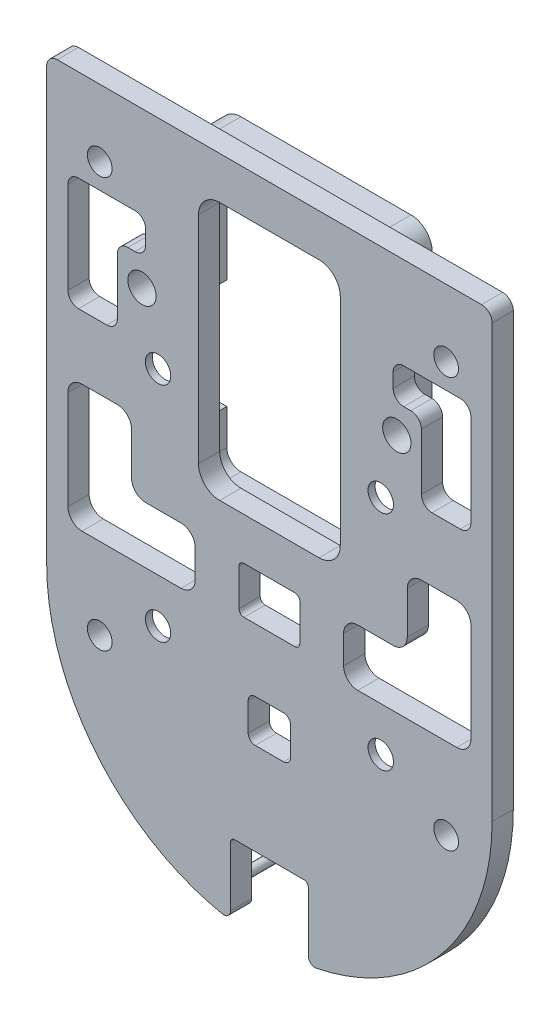
SolidWorks part; units mm, degrees
ref_plane "Alzado" through (0, 0, 0) normal (0, 0, 1) x (1, 0, 0)
ref_plane "Planta" through (0, 0, 0) normal (0, 1, 0) x (1, 0, 0)
ref_plane "Vista lateral" through (0, 0, 0) normal (1, 0, 0) x (0, 0, -1)
sketch "Croquis1" plane through (0, 0, 0) normal (0, 0, 1) x (1, 0, 0)
  line L0 (-31.5, 0) -> (31.5, 0) construction
  line L1 (31.5, -46.5) -> (-31.5, -46.5)
  line L2 (31.5, -45) -> (31.5, 45)
  line L3 (30, 46.5) -> (-30, 46.5)
  line L4 (-31.5, -45) -> (-31.5, 45)
  line L5 (-31.5, -45) -> (-31.5, -46.5)
  line L7 (17.25, -17.25) -> (-17.25, -17.25) construction
  line L8 (17.25, -17.25) -> (17.25, 17.25) construction
  line L9 (17.25, 17.25) -> (-17.25, 17.25) construction
  line L10 (-17.25, -17.25) -> (-17.25, 17.25) construction
  line L11 (17.25, -17.25) -> (-17.25, 17.25) construction
  line L12 (17.25, 17.25) -> (-17.25, -17.25) construction
  line L13 (31.5, -45) -> (31.5, -46.5)
  line L14 (0, 46.5) -> (0, -46.5) construction
  circle A0 centre (-15.75, 15.75) radius 1.5
  arc A6 (31.5, 45) -> (30, 46.5) centre (30, 45) ccw
  arc A7 (-31.5, 45) -> (-30, 46.5) centre (-30, 45) cw
  circle A8 centre (15.75, 15.75) radius 1.5
  circle A9 centre (-15.75, -15.75) radius 1.5
  circle A10 centre (15.75, -15.75) radius 1.5
  point P0 (0, 0)
  point P6 (0, 0)
  point P13 (-15.75, 17.25)
  point P14 (-17.25, 15.75)
  point P15 (-17.25, 15.75)
  point P16 (0, 0)
  point P38 (0, 0)
  dimension "D4" = 3
  dimension "D5" = 31.5
  dimension "D7" = 1.5
  dimension "D1" = 60
  dimension "D2" = 31.5
  dimension "D3" = 90
  dimension "D6" = 93
extrude "Saliente-Extruir1" add sketch "Croquis1" along normal blind 3
sketch "Croquis3" plane through (0, 0, 3) normal (0, 0, 1) x (1, 0, 0)
  line L0 (0, 46.5) -> (0, -46.5) construction
  line L1 (2, -17.5) -> (-2, -17.5)
  line L2 (-9, -45.5) -> (9, -45.5) construction
  line L3 (-9, -45.5) -> (-9, -2.3) construction
  line L4 (-9, -2.3) -> (9, -2.3) construction
  line L5 (9, -45.5) -> (9, -2.3) construction
  line L7 (0, -2.3) -> (0, -45.5) construction
  line L8 (-3.6, -2.3) -> (3.6, -2.3)
  line L9 (-4, -2.7) -> (-4, -7.9)
  line L10 (-3.6, -8.3) -> (3.6, -8.3)
  line L11 (4, -2.7) -> (4, -7.9)
  line L12 (-9, -23.9) -> (9, -23.9) construction
  line L13 (-31.5, -46.5) -> (31.5, -46.5) construction
  line L14 (3, -18.5) -> (3, -22.5)
  line L15 (-4.9, -47.5) -> (4.9, -47.5)
  line L16 (-5.5, -46.9) -> (-5.5, -37.1)
  line L17 (-4.9, -36.5) -> (4.9, -36.5)
  line L18 (5.5, -46.9) -> (5.5, -37.1)
  line L19 (2, -23.5) -> (-2, -23.5)
  line L20 (-3, -18.5) -> (-3, -22.5)
  line L24 (-31.5, -46.5) -> (31.5, -46.5)
  line L25 (-31.5, 45) -> (-31.5, -46.5)
  line L26 (30, 46.5) -> (-30, 46.5)
  line L27 (31.5, -46.5) -> (31.5, 45)
  line L28 (-31.5, -46.5) -> (31.5, -46.5) construction
  line L29 (-31.5, 45) -> (-31.5, -46.5) construction
  line L30 (30, 46.5) -> (-30, 46.5) construction
  line L31 (31.5, -46.5) -> (31.5, 45) construction
  circle A0 centre (-7.62, -3.68) radius 0.65
  circle A1 centre (7.62, -3.68) radius 0.65
  circle A2 centre (-7.62, -44.12) radius 0.65
  circle A3 centre (7.62, -44.12) radius 0.65
  arc A4 (4, -2.7) -> (3.6, -2.3) centre (3.6, -2.7) ccw
  arc A5 (4, -7.9) -> (3.6, -8.3) centre (3.6, -7.9) cw
  arc A6 (-3.6, -8.3) -> (-4, -7.9) centre (-3.6, -7.9) cw
  arc A7 (-4, -2.7) -> (-3.6, -2.3) centre (-3.6, -2.7) cw
  arc A8 (-5.5, -37.1) -> (-4.9, -36.5) centre (-4.9, -37.1) cw
  arc A9 (4.9, -36.5) -> (5.5, -37.1) centre (4.9, -37.1) cw
  arc A10 (5.5, -46.9) -> (4.9, -47.5) centre (4.9, -46.9) cw
  arc A11 (-4.9, -47.5) -> (-5.5, -46.9) centre (-4.9, -46.9) cw
  arc A12 (-3, -18.5) -> (-2, -17.5) centre (-2, -18.5) cw
  arc A13 (-2, -23.5) -> (-3, -22.5) centre (-2, -22.5) cw
  arc A14 (3, -22.5) -> (2, -23.5) centre (2, -22.5) cw
  arc A15 (3, -18.5) -> (2, -17.5) centre (2, -18.5) ccw
  arc A22 (-30, 46.5) -> (-31.5, 45) centre (-30, 45) ccw
  arc A23 (31.5, 45) -> (30, 46.5) centre (30, 45) ccw
  arc A26 (-30, 46.5) -> (-31.5, 45) centre (-30, 45) ccw construction
  arc A27 (31.5, 45) -> (30, 46.5) centre (30, 45) ccw construction
  point P16 (0, -2.3)
  point P35 (-4, -2.3)
  point P42 (5.5, -36.5)
  point P45 (5.5, -47.5)
  point P48 (-5.5, -47.5)
  line M6 (-31.5, -46.5) -> (31.5, -46.5)
  dimension "D6" = 1.3
  dimension "D9" = 0.4
  dimension "D15" = 0.6
  dimension "D16" = 0.6
  dimension "D21" = 1
  dimension "D1" = 1
  dimension "D2" = 18
  dimension "D4" = 6
  dimension "D5" = 8
  dimension "D7" = 1.38
  dimension "D8" = 1.38
  dimension "D10" = 43.2
  dimension "D11" = 11
  dimension "D12" = 9
  dimension "D13" = 11
  dimension "D14" = 5.5
  dimension "D17" = 28
  dimension "D18" = 12
  dimension "D19" = 22
  dimension "D20" = 12
  dimension "D22" = 0
extrude "Cortar-Extruir1" cut sketch "Croquis3" against normal through all contours A3 | L11 L8 L9 L10 | A11 L15 A10 L18 L16 M6 | A9 L17 A8 L16 L18 M6 | A2 | A0 | A1 | L19 A13 L20 A12 L1 A15 L14 A14 region at (0, -5.3, 3) region at (0, -46.9948, 3) region at (0, -41.5068, 3) region at (7.62, -44.12, 3)
sketch "Croquis5" plane through (0, 0, 3) normal (0, 0, 1) x (1, 0, 0)
  line L12 (4, -2.7) -> (4, -7.9) construction
  line L13 (-3.6, -2.3) -> (3.6, -2.3) construction
  line L14 (-4, -2.7) -> (-4, -7.9) construction
  line L15 (-3.6, -8.3) -> (3.6, -8.3) construction
  line L16 (4, -2.7) -> (4, -7.9)
  line L17 (-3.6, -2.3) -> (3.6, -2.3)
  line L18 (-4, -2.7) -> (-4, -7.9)
  line L19 (-3.6, -8.3) -> (3.6, -8.3)
  line L20 (4.3, -2.7) -> (4.3, -7.9)
  line L21 (-3.6, -8.6) -> (3.6, -8.6)
  line L22 (-4.3, -2.7) -> (-4.3, -7.9)
  line L23 (-3.6, -2) -> (3.6, -2)
  circle A0 centre (7.62, -44.12) radius 0.65 construction
  circle A1 centre (-7.62, -44.12) radius 0.65 construction
  circle A8 centre (7.62, -44.12) radius 0.65
  circle A9 centre (-7.62, -44.12) radius 0.65
  arc A37 (4, -2.7) -> (3.6, -2.3) centre (3.6, -2.7) ccw construction
  arc A38 (3.6, -8.3) -> (4, -7.9) centre (3.6, -7.9) ccw construction
  arc A39 (-4, -7.9) -> (-3.6, -8.3) centre (-3.6, -7.9) ccw construction
  arc A40 (-3.6, -2.3) -> (-4, -2.7) centre (-3.6, -2.7) ccw construction
  circle A41 centre (-7.62, -3.68) radius 0.65 construction
  circle A42 centre (7.62, -3.68) radius 0.65 construction
  circle A43 centre (-15.75, -15.75) radius 1.5 construction
  circle A44 centre (15.75, -15.75) radius 1.5 construction
  circle A45 centre (15.75, 15.75) radius 1.5 construction
  circle A46 centre (-15.75, 15.75) radius 1.5 construction
  arc A47 (4, -2.7) -> (3.6, -2.3) centre (3.6, -2.7) ccw
  arc A48 (3.6, -8.3) -> (4, -7.9) centre (3.6, -7.9) ccw
  arc A49 (-4, -7.9) -> (-3.6, -8.3) centre (-3.6, -7.9) ccw
  arc A50 (-3.6, -2.3) -> (-4, -2.7) centre (-3.6, -2.7) ccw
  circle A51 centre (-7.62, -3.68) radius 0.65
  circle A52 centre (7.62, -3.68) radius 0.65
  circle A53 centre (-15.75, -15.75) radius 1.5
  circle A54 centre (15.75, -15.75) radius 1.5
  circle A55 centre (15.75, 15.75) radius 1.5
  circle A56 centre (-15.75, 15.75) radius 1.5
  arc A57 (3.6, -8.6) -> (4.3, -7.9) centre (3.6, -7.9) ccw
  arc A58 (-4.3, -7.9) -> (-3.6, -8.6) centre (-3.6, -7.9) ccw
  arc A59 (-3.6, -2) -> (-4.3, -2.7) centre (-3.6, -2.7) ccw
  arc A60 (4.3, -2.7) -> (3.6, -2) centre (3.6, -2.7) ccw
  circle A63 centre (-15.75, -15.75) radius 1.8
  circle A64 centre (15.75, -15.75) radius 1.8
  circle A65 centre (15.75, 15.75) radius 1.8
  circle A66 centre (-15.75, 15.75) radius 1.8
  dimension "D1" = 0.3
extrude "Cortar-Extruir3" cut sketch "Croquis5" against normal through all
fillet "Redondeo1" radius 1 2 edges at (5.5, -46.5, 1.5) (-5.5, -46.5, 1.5)
sketch "Croquis14" plane through (0, 0, 0) normal (0, 0, -1) x (-1, 0, 0)
  circle A0 centre (7.62, -44.12) radius 0.65 construction
  circle A1 centre (-7.62, -44.12) radius 0.65 construction
  circle A2 centre (7.62, -3.68) radius 0.65 construction
  circle A3 centre (-7.62, -3.68) radius 0.65 construction
  circle A4 centre (7.62, -44.12) radius 0.65
  circle A5 centre (-7.62, -44.12) radius 0.65
  circle A6 centre (7.62, -3.68) radius 0.65
  circle A7 centre (-7.62, -3.68) radius 0.65
extrude "Saliente-Extruir2" add sketch "Croquis14" along normal blind 5 and the other way up to surface (3 mm away) other way up to face at (0, -5.3, 3)
sketch "Croquis18" plane through (0, 0, 0) normal (0, 0, -1) x (-1, 0, 0)
  line L0 (0, 46.5) -> (0, -46.5) construction
  line L1 (12.025, 1) -> (-12.025, 1)
  line L2 (14.025, 3) -> (14.025, 41.5)
  line L3 (12.025, 43.5) -> (-12.025, 43.5)
  line L4 (-14.025, 3) -> (-14.025, 41.5)
  line L5 (14.025, 1) -> (-14.025, 43.5) construction
  line L6 (14.025, 43.5) -> (-14.025, 1) construction
  line L7 (-15.025, 3) -> (-15.025, 41.5)
  line L8 (12.025, 44.5) -> (-12.025, 44.5)
  line L9 (15.025, 3) -> (15.025, 41.5)
  line L10 (12.025, 0) -> (-12.025, 0)
  line L11 (-30, 46.5) -> (30, 46.5) construction
  arc A0 (12.025, 43.5) -> (14.025, 41.5) centre (12.025, 41.5) cw
  arc A1 (14.025, 3) -> (12.025, 1) centre (12.025, 3) cw
  arc A2 (-12.025, 1) -> (-14.025, 3) centre (-12.025, 3) cw
  arc A3 (-12.025, 43.5) -> (-14.025, 41.5) centre (-12.025, 41.5) ccw
  arc A4 (-12.025, 44.5) -> (-15.025, 41.5) centre (-12.025, 41.5) ccw
  arc A5 (12.025, 44.5) -> (15.025, 41.5) centre (12.025, 41.5) cw
  arc A6 (15.025, 3) -> (12.025, 0) centre (12.025, 3) cw
  arc A7 (-12.025, 0) -> (-15.025, 3) centre (-12.025, 3) cw
  point P0 (0, 22.25)
  dimension "D3" = 2
  dimension "D1" = 28.05
  dimension "D2" = 42.5
  dimension "D5" = 2
  dimension "D4" = 1
extrude "Saliente-Extruir3" add sketch "Croquis18" along normal blind 5
sketch "Croquis22" plane through (0, 0, 0) normal (0, 0, -1) x (-1, 0, 0)
  line L0 (-14.025, 41.5) -> (-14.025, 16.2642) construction
  line L1 (12.025, 43.5) -> (-12.025, 43.5) construction
  line L2 (-12.025, 1) -> (12.025, 1) construction
  line L3 (14.025, 3) -> (14.025, 15.2358) construction
  line L4 (-14.025, 41.5) -> (-14.025, 16.2642) construction
  line L5 (12.025, 43.5) -> (-12.025, 43.5) construction
  line L6 (-12.025, 1) -> (12.025, 1) construction
  line L7 (14.025, 3) -> (14.025, 15.2358) construction
  line L8 (18.025, 24.5) -> (-18.025, 24.5) construction
  line L9 (15.025, 3) -> (15.025, 14.1025) construction
  line L10 (-15.025, 41.5) -> (-15.025, 17.3975) construction
  circle A0 centre (18.025, 24.5) radius 2
  circle A1 centre (-18.025, 24.5) radius 2
  dimension "D1" = 4
  dimension "D2" = 4
  dimension "D3" = 3
  dimension "D4" = 3
  dimension "D5" = 19
extrude "Cortar-Extruir14" cut sketch "Croquis22" against normal blind 30
sketch "Croquis16" plane through (0, 0, 0) normal (0, 0, -1) x (-1, 0, 0)
  circle A0 centre (15.75, -15.75) radius 1.8 construction
  circle A1 centre (-15.75, -15.75) radius 1.8 construction
  circle A2 centre (-15.75, 15.75) radius 1.8 construction
  circle A3 centre (15.75, 15.75) radius 1.8 construction
  circle A4 centre (15.75, -15.75) radius 1.8
  circle A5 centre (-15.75, -15.75) radius 1.8
  circle A6 centre (-15.75, 15.75) radius 1.8
  circle A7 centre (15.75, 15.75) radius 1.8
  circle A8 centre (15.75, -15.75) radius 4.8
  circle A9 centre (-15.75, -15.75) radius 4.8
  circle A10 centre (-15.75, 15.75) radius 4.8
  circle A11 centre (15.75, 15.75) radius 4.8
  dimension "D1" = 3
extrude "Cortar-Extruir9" cut sketch "Croquis16" against normal blind 2 and the other way blind 30
sketch "Croquis23" plane through (0, 0, -5) normal (0, 0, -1) x (-1, 0, 0)
  line L0 (15.025, 23.4949) -> (-15.025, 23.4949) construction
  line L1 (15.025, 20.4949) -> (15.025, 41.5) construction
  line L2 (-15.025, 41.5) -> (-15.025, 20.4949) construction
  line L3 (-15.025, 23.4949) -> (-15.025, 16.6219) construction
  line L4 (-15.025, 11.0051) -> (-15.025, 3) construction
  line L5 (-15.025, 8.0051) -> (15.025, 8.0051) construction
  line L6 (15.025, 3) -> (15.025, 11.0051) construction
  line L7 (15.025, 8.0051) -> (15.025, 14.8781) construction
  line L8 (-14.025, 8.0051) -> (-15.025, 8.0051)
  line L9 (-14.025, 20.2293) -> (-14.025, 41.5) construction
  line L10 (-15.025, 17.3975) -> (-15.025, 14.1025) construction
  line L11 (14.025, 41.5) -> (14.025, 20.2293) construction
  line L12 (14.025, 11.2707) -> (14.025, 3) construction
  line L13 (-14.025, 15.2358) -> (-14.025, 16.2642) construction
  line L14 (-14.025, 3) -> (-14.025, 11.2707) construction
  line L15 (14.025, 16.2642) -> (14.025, 15.2358) construction
  line L16 (15.025, 20.4949) -> (15.025, 23.4949)
  line L18 (-15.025, 23.4949) -> (-15.025, 20.4949)
  line L19 (-14.025, 20.2293) -> (-14.025, 23.4949)
  line L21 (14.025, 23.4949) -> (14.025, 20.2293)
  line L22 (14.025, 11.2707) -> (14.025, 8.0051)
  line L24 (-14.025, 8.0051) -> (-14.025, 11.2707)
  line L25 (-15.025, 11.0051) -> (-15.025, 8.0051)
  line L27 (15.025, 8.0051) -> (15.025, 11.0051)
  line L28 (15.025, 8.0051) -> (14.025, 8.0051)
  line L29 (15.025, 23.4949) -> (14.025, 23.4949)
  line L30 (-14.025, 23.4949) -> (-15.025, 23.4949)
  line L31 (15.025, 14.1025) -> (15.025, 17.3975) construction
  line L36 (15.025, 16.9698) -> (15.025, 23.4949) construction
  line L37 (-15.025, 14.5302) -> (-15.025, 8.0051) construction
  line L42 (-15.025, 17.3975) -> (-15.025, 14.1025)
  line L43 (-14.025, 15.2358) -> (-14.025, 16.2642)
  line L44 (14.025, 16.2642) -> (14.025, 15.2358)
  line L45 (15.025, 14.1025) -> (15.025, 17.3975)
  arc A0 (15.025, 20.4949) -> (14.025, 20.2293) centre (15.75, 15.75) ccw construction
  arc A1 (-15.025, 14.1025) -> (-14.025, 15.2358) centre (-15.75, 15.75) ccw construction
  arc A2 (-14.025, 16.2642) -> (-15.025, 17.3975) centre (-15.75, 15.75) ccw construction
  arc A3 (-14.025, 20.2293) -> (-15.025, 20.4949) centre (-15.75, 15.75) ccw construction
  arc A4 (14.025, 15.2358) -> (15.025, 14.1025) centre (15.75, 15.75) ccw construction
  arc A5 (15.025, 17.3975) -> (14.025, 16.2642) centre (15.75, 15.75) ccw construction
  arc A6 (14.025, 11.2707) -> (15.025, 11.0051) centre (15.75, 15.75) ccw construction
  arc A9 (-15.025, 11.0051) -> (-14.025, 11.2707) centre (-15.75, 15.75) ccw construction
  arc A12 (15.025, 20.4949) -> (14.025, 20.2293) centre (15.75, 15.75) ccw
  arc A15 (-14.025, 20.2293) -> (-15.025, 20.4949) centre (-15.75, 15.75) ccw
  arc A18 (14.025, 11.2707) -> (15.025, 11.0051) centre (15.75, 15.75) ccw
  arc A21 (-15.025, 11.0051) -> (-14.025, 11.2707) centre (-15.75, 15.75) ccw
  arc A26 (-15.025, 14.1025) -> (-14.025, 15.2358) centre (-15.75, 15.75) ccw
  arc A27 (-14.025, 16.2642) -> (-15.025, 17.3975) centre (-15.75, 15.75) ccw
  arc A28 (14.025, 15.2358) -> (15.025, 14.1025) centre (15.75, 15.75) ccw
  arc A29 (15.025, 17.3975) -> (14.025, 16.2642) centre (15.75, 15.75) ccw
  dimension "D1" = 3
  dimension "D2" = 3
extrude "Cortar-Extruir15" cut sketch "Croquis23" against normal up to surface (5 mm away) up to face at (-10.95, -15.75, 0)
sketch "Croquis11" plane through (0, 0, 3) normal (0, 0, 1) x (1, 0, 0)
  line L0 (0.5, 14.5) -> (0.5, -22.5) construction
  line L1 (-25.5, 8) -> (26.5, 8) construction
  line L2 (-31.5, -46.5) -> (31.5, -46.5) construction
  line L3 (-25.5, 38.5) -> (26.5, 38.5) construction
  line L4 (-25.5, 38.5) -> (-25.5, -22.5) construction
  line L5 (-25.5, -22.5) -> (26.5, -22.5) construction
  line L6 (26.5, 38.5) -> (26.5, -22.5) construction
  line L8 (-31.5, 45) -> (-31.5, -46.5) construction
  line L9 (-25.5, 38.5) -> (-28, 38.5) construction
  line L10 (-25.5, 38.5) -> (-25.5, 23) construction
  circle A1 centre (-24, 37) radius 1.5 construction
  circle A2 centre (25, 37) radius 1.5 construction
  circle A3 centre (25, -21) radius 1.5 construction
  circle A8 centre (-24, -21) radius 1.5 construction
  circle A12 centre (-24, 37) radius 1.75
  circle A14 centre (25, -21) radius 1.75
  circle A15 centre (25, 37) radius 1.75
  circle A16 centre (-24, -21) radius 1.75
  point P10 (0.5, -4)
  point P15 (0.5, 38.5)
  point P24 (-24, 38.5)
  point P28 (-3.25, 24.75)
  point P29 (-25.5, 37)
  dimension "D7" = 0.25
  dimension "D6" = 3
  dimension "D1" = 58
  dimension "D2" = 52
  dimension "D3" = 85
  dimension "D4" = 6
  dimension "D5" = 0.25
  dimension "D8" = 0.25
  dimension "D9" = 0.25
extrude "Cortar-Extruir6" cut sketch "Croquis11" against normal blind 52 contours A15 | A14 | A16 | A12
sketch "Croquis24" plane through (0, 0, 0) normal (0, 0, -1) x (-1, 0, 0)
  line L0 (-12.025, 1) -> (12.025, 1) construction
  line L1 (7.025, 4) -> (-7.025, 4)
  line L2 (10.025, 7) -> (10.025, 37.5)
  line L3 (7.025, 40.5) -> (-7.025, 40.5)
  line L4 (-10.025, 7) -> (-10.025, 37.5)
  line L5 (26.5, -9.5) -> (12.5, -9.5)
  line L6 (28.5, -7.5) -> (28.5, -3.4761)
  line L7 (17.5, -1.5) -> (12.5, -1.5)
  line L8 (10.5, -7.5) -> (10.5, -3.5)
  line L10 (28.5, -3.4761) -> (28.5, 6.5)
  line L11 (26.5, 8.5) -> (21.5, 8.5)
  line L12 (19.5, 0.5) -> (19.5, 6.5)
  line L21 (14.025, 3) -> (14.025, 8.0051) construction
  line L22 (-14.025, 8.0051) -> (-14.025, 3) construction
  line L23 (12.025, 43.5) -> (-12.025, 43.5) construction
  line L25 (31.5, 45) -> (31.5, -46.5) construction
  line L28 (0, -47.0419) -> (0, 46.5) construction
  line L29 (-30, 46.5) -> (30, 46.5) construction
  line L30 (-28.5, 32) -> (-28.5, 19)
  line L31 (-27, 17.5) -> (-23, 17.5)
  line L32 (-21.5, 19) -> (-21.5, 27)
  line L33 (-20, 28.5) -> (-19, 28.5)
  line L34 (-17.5, 30) -> (-17.5, 32)
  line L35 (-19, 33.5) -> (-27, 33.5)
  line L37 (19, 33.5) -> (27, 33.5)
  line L38 (-26.5, -9.5) -> (-12.5, -9.5)
  line L39 (-10.5, -7.5) -> (-10.5, -3.5)
  line L40 (-17.5, -1.5) -> (-12.5, -1.5)
  line L41 (-19.5, 0.5) -> (-19.5, 6.5)
  line L42 (-26.5, 8.5) -> (-21.5, 8.5)
  line L43 (-28.5, -3.4761) -> (-28.5, 6.5)
  line L44 (-28.5, -7.5) -> (-28.5, -3.4761)
  line L45 (0, 46.5) -> (0, -46.5) construction
  line L46 (17.5, 30) -> (17.5, 32)
  line L47 (20, 28.5) -> (19, 28.5)
  line L48 (21.5, 19) -> (21.5, 27)
  line L49 (27, 17.5) -> (23, 17.5)
  line L50 (28.5, 32) -> (28.5, 19)
  arc A0 (-10.025, 7) -> (-7.025, 4) centre (-7.025, 7) ccw
  arc A1 (-10.025, 37.5) -> (-7.025, 40.5) centre (-7.025, 37.5) cw
  arc A2 (7.025, 40.5) -> (10.025, 37.5) centre (7.025, 37.5) cw
  arc A3 (10.025, 7) -> (7.025, 4) centre (7.025, 7) cw
  arc A4 (-28.5, 32) -> (-27, 33.5) centre (-27, 32) cw
  arc A5 (-17.5, 32) -> (-19, 33.5) centre (-19, 32) ccw
  arc A6 (-19, 28.5) -> (-17.5, 30) centre (-19, 30) ccw
  arc A7 (-21.5, 27) -> (-20, 28.5) centre (-20, 27) cw
  arc A8 (-23, 17.5) -> (-21.5, 19) centre (-23, 19) ccw
  arc A9 (26.5, -9.5) -> (28.5, -7.5) centre (26.5, -7.5) ccw
  arc A10 (26.5, 8.5) -> (28.5, 6.5) centre (26.5, 6.5) cw
  arc A11 (21.5, 8.5) -> (19.5, 6.5) centre (21.5, 6.5) ccw
  arc A12 (19.5, 0.5) -> (17.5, -1.5) centre (17.5, 0.5) cw
  arc A13 (10.5, -3.5) -> (12.5, -1.5) centre (12.5, -3.5) cw
  arc A14 (10.5, -7.5) -> (12.5, -9.5) centre (12.5, -7.5) ccw
  arc A15 (-28.5, 19) -> (-27, 17.5) centre (-27, 19) ccw
  arc A16 (28.5, 19) -> (27, 17.5) centre (27, 19) cw
  arc A17 (23, 17.5) -> (21.5, 19) centre (23, 19) cw
  arc A18 (21.5, 27) -> (20, 28.5) centre (20, 27) ccw
  arc A19 (19, 28.5) -> (17.5, 30) centre (19, 30) cw
  arc A20 (17.5, 32) -> (19, 33.5) centre (19, 32) cw
  arc A21 (28.5, 32) -> (27, 33.5) centre (27, 32) ccw
  arc A22 (-10.5, -7.5) -> (-12.5, -9.5) centre (-12.5, -7.5) cw
  arc A23 (-10.5, -3.5) -> (-12.5, -1.5) centre (-12.5, -3.5) ccw
  arc A24 (-19.5, 0.5) -> (-17.5, -1.5) centre (-17.5, 0.5) ccw
  arc A25 (-21.5, 8.5) -> (-19.5, 6.5) centre (-21.5, 6.5) cw
  arc A26 (-26.5, 8.5) -> (-28.5, 6.5) centre (-26.5, 6.5) ccw
  arc A27 (-26.5, -9.5) -> (-28.5, -7.5) centre (-26.5, -7.5) cw
  point P27 (-28.5, 33.5)
  point P58 (-28.5, 17.5)
  point P82 (28.5, 17.5)
  point P83 (28.5, 33.5)
  dimension "D1" = 3
  dimension "D2" = 13
  dimension "D13" = 2
  dimension "D10" = 1.5
  dimension "D3" = 3
  dimension "D4" = 4
  dimension "D5" = 4
  dimension "D6" = 3
  dimension "D7" = 5
  dimension "D8" = 7
  dimension "D9" = 16
  dimension "D11" = 11
  dimension "D12" = 9
  dimension "D14" = 3
  dimension "D15" = 18
  dimension "D16" = 8
  dimension "D17" = 18
  dimension "D18" = 9
extrude "Cortar-Extruir16" cut sketch "Croquis24" against normal blind 30 contours A27 L38 A22 L39 A23 L40 A24 L41 A25 L42 A26 L43 L44 | L8 A14 L5 A9 L6 L10 A10 L11 A11 L12 A12 L7 A13 | L1 L28 L3 A1 L4 A0 | L28 L1 A3 L2 A2 L3 | L30 A15 L31 A8 L32 A7 L33 A6 L34 A5 L35 A4 | L50 A21 L37 A20 L46 A19 L47 A18 L48 A17 L49 A16 region at (-4.9662, 22.25, 0) region at (4.9662, 22.25, 0) region at (-21.2532, -2.058, 0) region at (24.1815, 26.3432, 0) region at (-24.1815, 26.3432, 0) region at (21.2532, -2.058, 0)
fillet "Redondeo2" radius 31 2 edges at (-31.5, -46.5, 1.5) (31.5, -46.5, 1.5)
